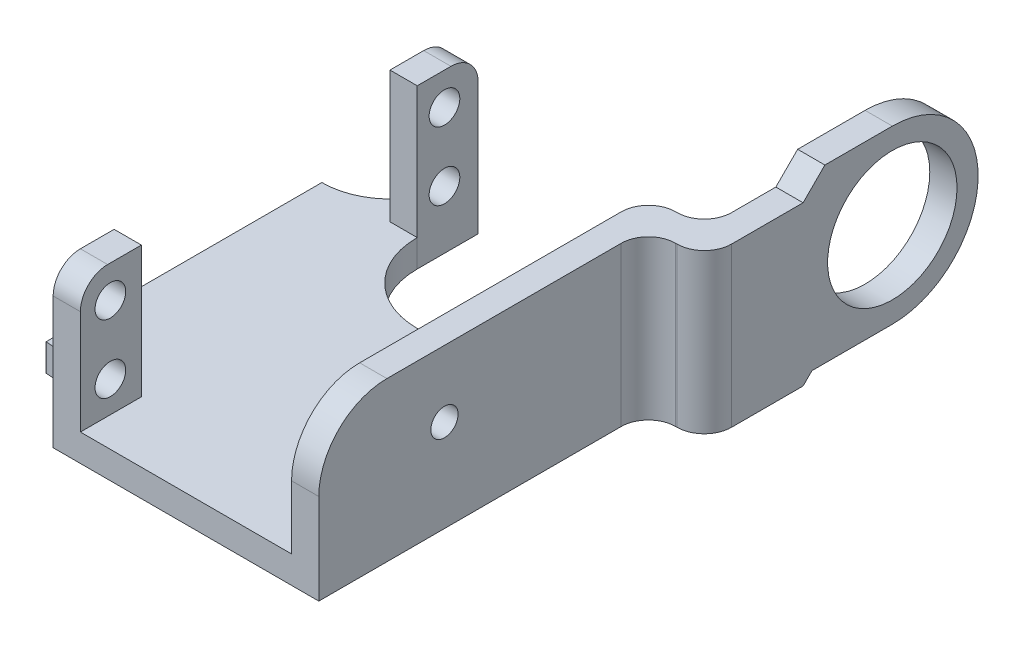
SolidWorks part; units mm, degrees
material "PLA"
ref_plane "Front Plane" through (0, 0, 0) normal (0, 0, 1) x (1, 0, 0)
ref_plane "Top Plane" through (0, 0, 0) normal (0, 1, 0) x (1, 0, 0)
ref_plane "Right Plane" through (0, 0, 0) normal (1, 0, 0) x (0, 0, -1)
sketch "Sketch1" plane through (0, 0, 0) normal (0, 1, 0) x (1, 0, 0)
  line L0 (-49, 49.45) -> (-39, 49.45)
  line L1 (-39, 49.45) -> (-39, 58.4)
  line L2 (-39, 58.4) -> (0, 58.4)
  line L3 (0, 58.4) -> (0, 0)
  line L4 (0, 0) -> (-39, 0)
  line L5 (-39, 0) -> (-39, 8.95)
  line L6 (-39, 8.95) -> (-49, 8.95)
  line L7 (-49, 8.95) -> (-49, 49.45)
  dimension "D1" = 58.4
  dimension "D2" = 49
  dimension "D3" = 10
  dimension "D4" = 8.95
  dimension "D5" = 8.95
extrude "Boss-Extrude1" add sketch "Sketch1" along normal blind 4
sketch "Sketch2" plane through (-39, 0, 0) normal (-1, 0, 0) x (0, 0, 1)
  line L0 (-58.4, 4) -> (-49.45, 4) construction
  line L1 (-8.95, 23.3) -> (0, 23.3)
  line L2 (-8.95, 23.3) -> (-8.95, 4)
  line L3 (-8.95, 4) -> (0, 4)
  line L4 (0, 23.3) -> (0, 4)
  line L5 (-58.4, 23.3) -> (-49.45, 23.3)
  line L6 (-58.4, 23.3) -> (-58.4, 4)
  line L7 (-58.4, 4) -> (-49.45, 4)
  line L8 (-49.45, 23.3) -> (-49.45, 4)
  line L9 (-58.4, 4) -> (-58.4, 0) construction
  line L10 (-49.45, 4) -> (-49.45, 0) construction
  line L11 (-8.95, 4) -> (0, 4) construction
  line L12 (0, 4) -> (0, 0) construction
  line L13 (-8.95, 4) -> (-8.95, 0) construction
  line L14 (-49.45, 4) -> (-8.95, 4) construction
  circle A0 centre (-4.4, 18.55) radius 2.25
  circle A1 centre (-4.4, 8.55) radius 2.25
  circle A2 centre (-53.45, 18.55) radius 2.25
  circle A3 centre (-53.45, 8.55) radius 2.25
  dimension "D1" = 4.5
  dimension "D2" = 4.5
  dimension "D8" = 4.5
  dimension "D9" = 4.5
  dimension "D3" = 19.3
  dimension "D4" = 10
  dimension "D5" = 4
  dimension "D6" = 4.55
  dimension "D7" = 4
  dimension "D10" = 4.55
extrude "Boss-Extrude2" add sketch "Sketch2" against normal blind 4
fillet "Fillet1" radius 10 2 edges at (-39, 2, -49.45) (-39, 2, -8.95)
fillet "Fillet2" radius 4 2 edges at (-37, 23.3, -58.4) (-37, 23.3, 0)
sketch "Sketch3" plane through (0, 0, 0) normal (1, 0, 0) x (0, 0, -1)
  line L0 (0, 4) -> (58.4, 4) construction
  line L1 (0, 23.3) -> (52.4, 23.3)
  line L2 (0, 23.3) -> (0, 4)
  line L3 (0, 4) -> (52.4, 4)
  line L4 (52.4, 23.3) -> (52.4, 4)
  line L5 (0, 4) -> (0, 0) construction
  circle A0 centre (18.45, 13.55) radius 2
  dimension "D4" = 4
  dimension "D1" = 19.3
  dimension "D2" = 18.45
  dimension "D3" = 9.55
  dimension "D5" = 52.4
extrude "Boss-Extrude3" add sketch "Sketch3" against normal blind 4
fillet "Fillet3" radius 10 1 edges at (-2, 23.3, 0)
sketch "Sketch4" plane through (0, 4, 0) normal (0, 1, 0) x (1, 0, 0)
  line L0 (0, 58.4) -> (-35, 58.4) construction
  line L1 (-4, 58.4) -> (-35, 58.4)
  line L2 (-4, 58.4) -> (-4, 37.9)
  line L3 (-4, 37.9) -> (-35, 37.9)
  line L4 (-35, 58.4) -> (-35, 37.9)
  line L5 (-35, 58.4) -> (-35, 49.45) construction
  line L6 (-4, 0) -> (-4, 52.4) construction
  dimension "D1" = 20.5
extrude "Cut-Extrude1" cut sketch "Sketch4" against normal blind 10
sketch "Sketch5" plane through (0, 4, 0) normal (0, 1, 0) x (1, 0, 0)
  line L4 (0, 58.4) -> (-4, 58.4)
  line L5 (-4, 58.4) -> (-4, 52.4)
  line L6 (-4, 52.4) -> (0, 52.4)
  line L7 (0, 52.4) -> (0, 58.4)
  line L8 (0, 58.4) -> (-4, 58.4)
  line L9 (-4, 58.4) -> (-4, 52.4)
  line L10 (-4, 52.4) -> (0, 52.4)
  line L11 (0, 52.4) -> (0, 58.4)
  dimension "D1" = 0
extrude "Cut-Extrude2" cut sketch "Sketch5" against normal blind 10
fillet "Fillet4" radius 11.55 1 edges at (-35, 2, -37.9)
sketch "Sketch6" plane through (0, 0, 0) normal (0, -1, 0) x (1, 0, 0)
  line L0 (0, -48.4) -> (4.2, -48.4)
  line L4 (4.2, -52.4) -> (0, -52.4)
  line L5 (0, -52.4) -> (0, -48.4)
  line L6 (0, 0) -> (0, -52.4) construction
  line L7 (0, -52.4) -> (-4, -52.4) construction
  line L8 (4.2, -48.4) -> (4.2, -52.4)
  dimension "D1" = 4
extrude "Boss-Extrude4" add sketch "Sketch6" against normal up to surface (23.3 mm away) up to face at (-2, 23.3, -31.2)
sketch "Sketch7" plane through (4.2, 0, 0) normal (1, 0, 0) x (0, 0, -1)
  line L0 (48.4, 0) -> (48.4, 23.3)
  line L1 (48.4, 23.3) -> (62.9, 23.3)
  line L2 (62.9, 0) -> (48.4, 0)
  line L3 (48.4, 23.3) -> (48.4, 0) construction
  line L4 (52.4, 23.3) -> (48.4, 23.3) construction
  line L5 (52.4, 0) -> (48.4, 0) construction
  line L6 (76, 26.5) -> (66.1, 26.5)
  line L7 (66.1, 26.5) -> (62.9, 23.3)
  line L8 (62.9, 0) -> (64.2, 1.3)
  line L9 (64.2, 1.3) -> (76, 1.3)
  circle A0 centre (76, 13.9) radius 9.5
  arc A1 (76, 1.3) -> (76, 26.5) centre (76, 13.9) ccw
  dimension "D1" = 25.2
  dimension "D2" = 19
  dimension "D3" = 9.4
  dimension "D4" = 13.1
  dimension "D5" = 3.2
  dimension "D6" = 1.3
  dimension "D7" = 27.6
extrude "Boss-Extrude5" add sketch "Sketch7" along normal blind 4
fillet "Fillet6" radius 4 4 edges at (0, 11.65, -48.4) (-4, 11.65, -52.4) (4.2, 11.65, -52.4) (8.2, 11.65, -48.4)
